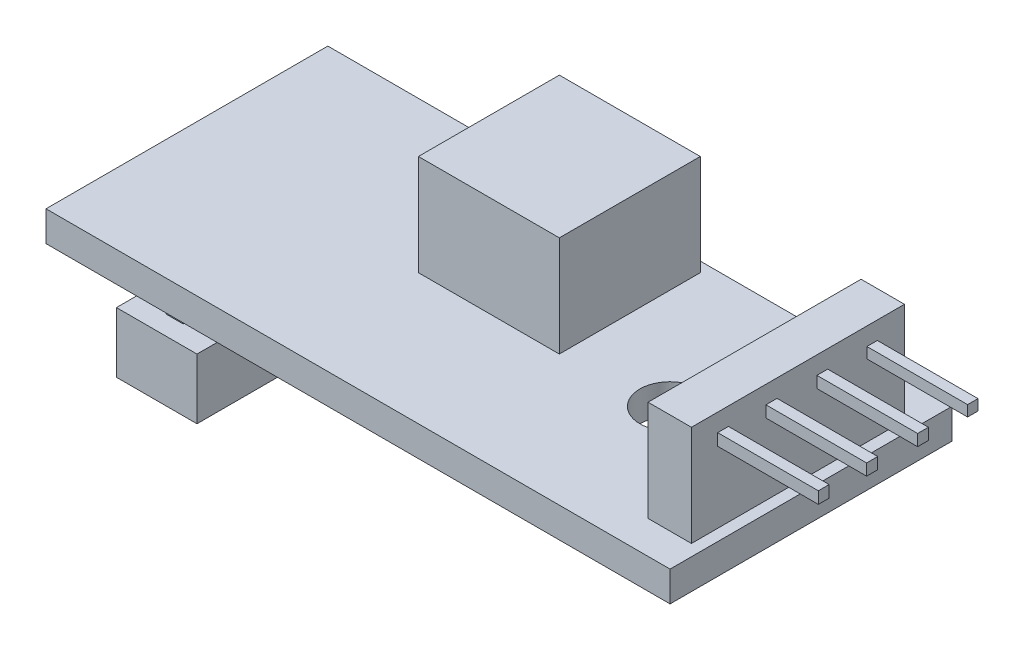
SolidWorks part; units mm, degrees
ref_plane "Front" through (0, 0, 0) normal (0, 0, 1) x (1, 0, 0)
ref_plane "Top" through (0, 0, 0) normal (0, 1, 0) x (1, 0, 0)
ref_plane "Right" through (0, 0, 0) normal (1, 0, 0) x (0, 0, -1)
sketch "草圖1" plane through (0, 0, 0) normal (0, 1, 0) x (1, 0, 0)
  line L1 (0, -7) -> (31, -7)
  line L2 (0, -7) -> (0, 7)
  line L3 (0, 7) -> (31, 7)
  line L4 (31, -7) -> (31, 7)
  dimension "D1" = 14
  dimension "D2" = 31
extrude "填料-伸長1" add sketch "草圖1" along normal blind 1.5
sketch "草圖2" plane through (0, 1.5, 0) normal (0, 1, 0) x (1, 0, 0)
  line L1 (12, 6.5) -> (19, 6.5)
  line L2 (12, 6.5) -> (12, -0.5)
  line L3 (12, -0.5) -> (19, -0.5)
  line L4 (19, 6.5) -> (19, -0.5)
  line L5 (31, 7) -> (0, 7) construction
  line L6 (0, 7) -> (0, -7) construction
  dimension "D1" = 7
  dimension "D2" = 7
  dimension "D3" = 0.5
  dimension "D4" = 12
extrude "填料-伸長2" add sketch "草圖2" along normal blind 5 separate body
sketch "草圖3" plane through (0, 1.5, 0) normal (0, 1, 0) x (1, 0, 0)
  line L1 (28.2749, 5.2139) -> (30.4297, 5.2139)
  line L2 (28.2749, 5.2139) -> (28.2749, -5.3678)
  line L3 (28.2749, -5.3678) -> (30.4297, -5.3678)
  line L4 (30.4297, 5.2139) -> (30.4297, -5.3678)
extrude "填料-伸長3" add sketch "草圖3" along normal blind 5 separate body
sketch "草圖5" plane through (30.4297, 0, 0) normal (1, 0, 0) x (0, 0, -1)
  line L1 (-4.063, 5.6149) -> (-3.5286, 5.6149)
  line L2 (-4.063, 5.6149) -> (-4.063, 5.0288)
  line L3 (-4.063, 5.0288) -> (-3.5286, 5.0288)
  line L4 (-3.5286, 5.6149) -> (-3.5286, 5.0288)
  line L5 (-1.6668, 5.6149) -> (-1.1152, 5.6149)
  line L6 (-1.6668, 5.6149) -> (-1.6668, 5.046)
  line L7 (-1.6668, 5.046) -> (-1.1152, 5.046)
  line L8 (-1.1152, 5.6149) -> (-1.1152, 5.046)
  line L9 (0.8673, 5.6149) -> (1.4017, 5.6149)
  line L10 (0.8673, 5.6149) -> (0.8673, 5.046)
  line L11 (0.8673, 5.046) -> (1.4017, 5.046)
  line L12 (1.4017, 5.6149) -> (1.4017, 5.046)
  line L13 (3.3496, 5.6149) -> (3.8668, 5.6149)
  line L14 (3.3496, 5.6149) -> (3.3496, 5.0805)
  line L15 (3.3496, 5.0805) -> (3.8668, 5.0805)
  line L16 (3.8668, 5.6149) -> (3.8668, 5.0805)
  point P16 (3.8668, 5.0633)
  point P17 (3.3496, 5.0805)
  point P18 (1.4017, 5.0116)
  point P19 (0.8673, 5.046)
  point P20 (-1.1152, 5.0805)
  point P21 (-1.6668, 5.046)
  point P22 (-3.5286, 5.0633)
  point P23 (-4.063, 5.0288)
extrude "填料-伸長4" add sketch "草圖5" along normal blind 5
sketch "草圖6" plane through (0, 0, 0) normal (0, -1, 0) x (1, 0, 0)
  line L0 (0, -7) -> (0, 7) construction
  line L1 (1.5, -5) -> (5.5, -5)
  line L2 (1.5, -5) -> (1.5, 5)
  line L3 (1.5, 5) -> (5.5, 5)
  line L4 (5.5, -5) -> (5.5, 5)
  line L5 (31, -7) -> (0, -7) construction
  line L6 (0, 7) -> (31, 7) construction
  dimension "D1" = 1.5
  dimension "D2" = 2
  dimension "D3" = 2
  dimension "D4" = 4
extrude "填料-伸長5" add sketch "草圖6" along normal blind 3 from offset 3 separate body
sketch "草圖7" plane through (0, 0, 0) normal (0, -1, 0) x (1, 0, 0)
  line L1 (3.0192, 4.0495) -> (3.8621, 4.0495)
  line L2 (3.0192, 4.0495) -> (3.0192, 3.3532)
  line L3 (3.0192, 3.3532) -> (3.8621, 3.3532)
  line L4 (3.8621, 4.0495) -> (3.8621, 3.3532)
  line L5 (3.0192, 1.6308) -> (3.8621, 1.6308)
  line L6 (3.0192, 1.6308) -> (3.0192, 0.9712)
  line L7 (3.0192, 0.9712) -> (3.8621, 0.9712)
  line L8 (3.8621, 1.6308) -> (3.8621, 0.9712)
  line L9 (3.0192, -1.0078) -> (3.8621, -1.0078)
  line L10 (3.0192, -1.0078) -> (3.0192, -1.7408)
  line L11 (3.0192, -1.7408) -> (3.8621, -1.7408)
  line L12 (3.8621, -1.0078) -> (3.8621, -1.7408)
  line L13 (3.0192, -3.3899) -> (3.8621, -3.3899)
  line L14 (3.0192, -3.3899) -> (3.0192, -4.1228)
  line L15 (3.0192, -4.1228) -> (3.8621, -4.1228)
  line L16 (3.8621, -3.3899) -> (3.8621, -4.1228)
extrude "填料-伸長6" add sketch "草圖7" along normal up to next separate body
sketch "草圖8" plane through (0, 1.5, 0) normal (0, 1, 0) x (1, 0, 0)
  line L0 (0, 0) -> (24, 0) construction
  circle A0 centre (24, 0) radius 1.5
  dimension "D1" = 3
  dimension "D2" = 24
extrude "除料-伸長1" cut sketch "草圖8" against normal blind 3
